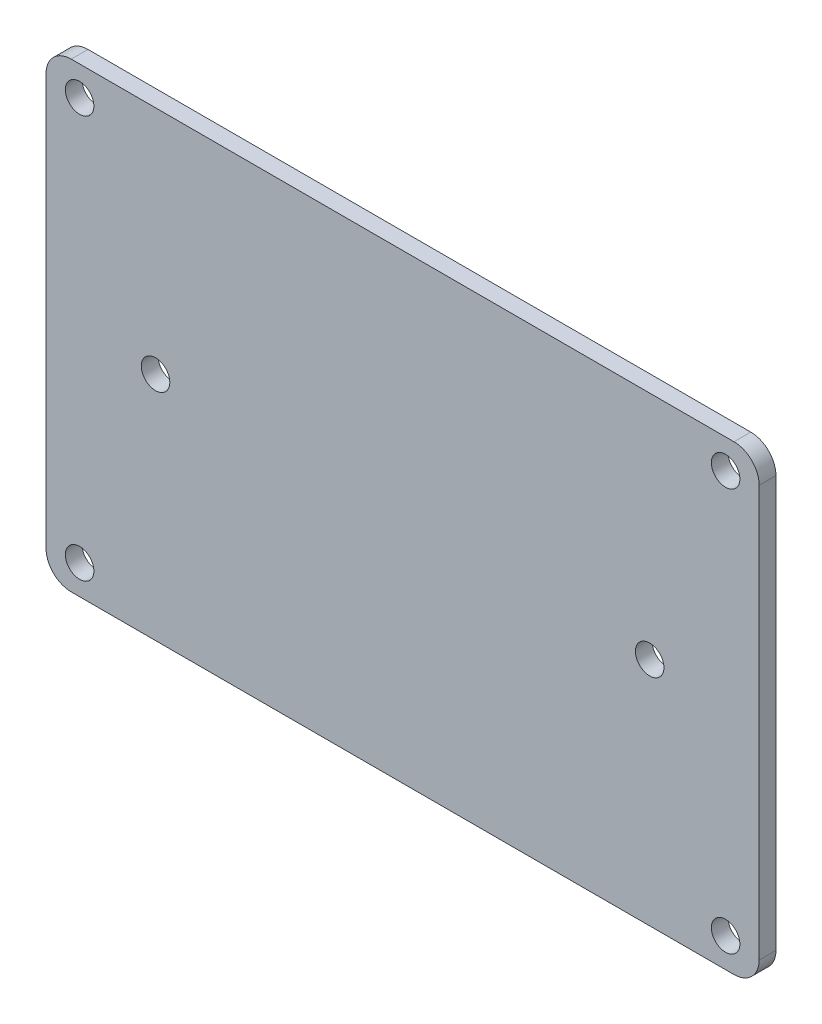
SolidWorks part; units mm, degrees
ref_plane "Front Plane" through (0, 0, 0) normal (0, 0, 1) x (1, 0, 0)
ref_plane "Top Plane" through (0, 0, 0) normal (0, 1, 0) x (1, 0, 0)
ref_plane "Right Plane" through (0, 0, 0) normal (1, 0, 0) x (0, 0, -1)
sketch "Sketch1" plane through (0, 0, 0) normal (0, 0, 1) x (1, 0, 0)
  line L0 (-38.5, 0) -> (0, 0) construction
  line L1 (-39.5, 27.5) -> (39.5, 27.5)
  line L2 (-42.5, 24.5) -> (-42.5, -24.5)
  line L3 (-39.5, -27.5) -> (39.5, -27.5)
  line L4 (42.5, 24.5) -> (42.5, -24.5)
  line L5 (-42.5, 27.5) -> (42.5, -27.5) construction
  line L6 (-42.5, -27.5) -> (42.5, 27.5) construction
  line L7 (-38.5, 0) -> (-38.5, -24) construction
  arc A3 (-39.5, 27.5) -> (-42.5, 24.5) centre (-39.5, 24.5) ccw
  arc A4 (-39.5, -27.5) -> (-42.5, -24.5) centre (-39.5, -24.5) cw
  arc A5 (42.5, -24.5) -> (39.5, -27.5) centre (39.5, -24.5) cw
  arc A6 (39.5, 27.5) -> (42.5, 24.5) centre (39.5, 24.5) cw
  circle A7 centre (-38.5, -24) radius 1.7
  point P0 (0, 0)
  dimension "D3" = 38.5
  dimension "D4" = 3.4
  dimension "D5" = 3
  dimension "D6" = 3
  dimension "D7" = 3
  dimension "D8" = 3
  dimension "D1" = 85
  dimension "D2" = 55
  dimension "D9" = 24
extrude "Boss-Extrude1" add sketch "Sketch1" along normal blind 2
sketch "Sketch3" plane through (0, 0, 0) normal (0, 0, 1) x (1, 0, 0)
  line L0 (0, 0) -> (38.5, 0) construction
  line L1 (38.5, 0) -> (38.5, -24) construction
  circle A1 centre (38.5, -24) radius 1.7
  dimension "D1" = 3.4
  dimension "D2" = 38.5
extrude "Cut-Extrude7" cut sketch "Sketch3" along normal up to next
sketch "Sketch4" plane through (0, 0, 2) normal (0, 0, 1) x (1, 0, 0)
  line L0 (0, 0) -> (-38.5, 0) construction
  line L1 (-38.5, 0) -> (-38.4978, 0.0203)
  line L2 (-38.5, 0) -> (-38.5, 24) construction
  circle A0 centre (-38.5, 24) radius 1.7
  dimension "D3" = 3.4
  dimension "D1" = 38.5
  dimension "D2" = 24
extrude "Cut-Extrude8" cut sketch "Sketch4" against normal through all contours A0 region at (-38.5, 24, 2)
sketch "Sketch7" plane through (0, 0, 2) normal (0, 0, 1) x (1, 0, 0)
  line L0 (0, 0) -> (38.5, 0) construction
  line L1 (38.5, 0) -> (38.5, 24) construction
  circle A0 centre (38.5, 24) radius 1.7
  dimension "D3" = 3.4
  dimension "D1" = 38.5
  dimension "D2" = 24
extrude "Cut-Extrude9" cut sketch "Sketch7" against normal through all contours A0 region at (38.5, 24, 2)
sketch "Sketch8" plane through (0, 0, 0) normal (0, 0, -1) x (-1, 0, 0)
  circle A0 centre (-29.45, 0) radius 1.7
  circle A1 centre (29.45, 0) radius 1.7
  dimension "D1" = 3.4
  dimension "D2" = 3.4
  dimension "D3" = 58.9
extrude "Cut-Extrude10" cut sketch "Sketch8" against normal up to next
